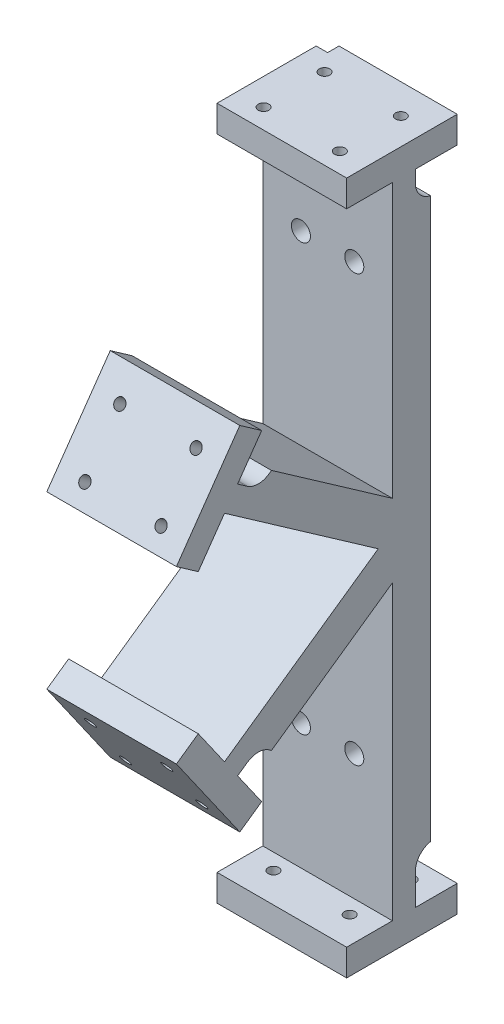
SolidWorks part; units mm, degrees
ref_plane "Front Plane" through (0, 0, 0) normal (0, 0, 1) x (1, 0, 0)
ref_plane "Top Plane" through (0, 0, 0) normal (0, 1, 0) x (1, 0, 0)
ref_plane "Right Plane" through (0, 0, 0) normal (1, 0, 0) x (0, 0, -1)
sketch "Sketch2" plane through (0, 0, 0) normal (0, 0, 1) x (1, 0, 0)
  line L1 (-73.75, 88.375) -> (73.75, 88.375)
  line L2 (-73.75, 88.375) -> (-73.75, -88.375)
  line L3 (-73.75, -88.375) -> (73.75, -88.375)
  line L4 (73.75, 88.375) -> (73.75, -88.375)
  line L5 (-73.75, 88.375) -> (73.75, -88.375) construction
  line L6 (-73.75, -88.375) -> (73.75, 88.375) construction
  point P0 (0, 0)
  dimension "D1" = 147.5
  dimension "D2" = 176.75
extrude "Boss-Extrude1" add sketch "Sketch2" along normal blind 10
sketch "Sketch3" plane through (-73.75, 0, 0) normal (-1, 0, 0) x (0, 0, 1)
  line L0 (0, 88.375) -> (0, -88.375) construction
  line L1 (-7, 88.375) -> (22, 88.375)
  line L2 (-7, 88.375) -> (-7, 73.375)
  line L3 (-7, 73.375) -> (22, 73.375)
  line L4 (22, 88.375) -> (22, 73.375)
  line L5 (10, 88.375) -> (10, -88.375) construction
  line L6 (0, 0) -> (56.8374, 0) construction
  line L7 (22, -88.375) -> (22, -73.375)
  line L8 (-7, -88.375) -> (-7, -73.375)
  line L9 (-7, -88.375) -> (22, -88.375)
  line L10 (-7, -73.375) -> (22, -73.375)
  line L11 (10, 88.375) -> (0, 88.375) construction
  dimension "D1" = 7
  dimension "D2" = 12
  dimension "D3" = 15
  dimension "D4" = 0
extrude "Boss-Extrude2" add sketch "Sketch3" against normal blind 34
ref_plane "Plane1" through (0, 0, 0) normal (1, 0, 0) x (0, 0, -1)
mirror "Mirror1" about plane through (0, 0, 0) normal (1, 0, 0) of "Boss-Extrude2"
sketch "Sketch5" plane through (-73.75, 0, 0) normal (-1, 0, 0) x (0, 0, 1)
  line L0 (10, 73.375) -> (10, -73.375) construction
  line L1 (-35, 0) -> (-35, 43.6802) construction
  line L2 (0, 0) -> (0, 73.375) construction
  line L3 (0, 0) -> (10, 0)
  line L4 (-35, 0) -> (0, 0) construction
  line L5 (-7, 88.375) -> (22, 88.375)
  line L6 (-7, 88.375) -> (-7, 73.375)
  line L7 (-7, 73.375) -> (22, 73.375)
  line L8 (22, 88.375) -> (22, 73.375)
  line L9 (0, 73.375) -> (10, 73.375)
  line L10 (0, 73.375) -> (0, 0)
  line L11 (0, 0) -> (10, 0)
  line L12 (10, 73.375) -> (10, 0)
  line L13 (5, 0) -> (5, -4.9122)
  line L18 (58.2224, 51.916) -> (50.0308, 46.1802)
  line L19 (-7, 73.375) -> (22, 73.375)
  line L20 (-7, 73.375) -> (-7, 63.375)
  line L21 (-7, 63.375) -> (22, 63.375)
  line L22 (22, 73.375) -> (22, 63.375)
  line L23 (50.0308, 46.1802) -> (66.6646, 22.4248)
  line L24 (58.2224, 51.916) -> (74.8561, 28.1606)
  line L25 (74.8561, 28.1606) -> (66.6646, 22.4248)
  line L26 (67.9732, 37.9904) -> (7.8679, -4.0958)
  line L27 (62.2374, 46.1819) -> (2.1321, 4.0958)
  line L28 (2.1321, 4.0958) -> (7.8679, -4.0958)
  line L29 (2.1321, -4.0958) -> (7.8679, 4.0958)
  line L30 (62.2374, -46.1819) -> (2.1321, -4.0958)
  line L31 (67.9732, -37.9904) -> (7.8679, 4.0958)
  line L32 (5, 0) -> (5, 4.9122)
  line L33 (74.8561, -28.1606) -> (66.6646, -22.4248)
  line L34 (58.2224, -51.916) -> (74.8561, -28.1606)
  line L35 (50.0308, -46.1802) -> (66.6646, -22.4248)
  line L36 (58.2224, -51.916) -> (50.0308, -46.1802)
  line L37 (50.0308, 46.1802) -> (66.6646, 22.4248)
  line L38 (-7, 63.375) -> (22, 63.375)
  line L39 (-7, 63.375) -> (-7, 48.375)
  line L40 (-7, 48.375) -> (22, 48.375)
  line L41 (22, 63.375) -> (22, 48.375)
  line L42 (50.0308, 46.1802) -> (37.7436, 37.5766)
  line L43 (37.7436, 37.5766) -> (54.3773, 13.8212)
  line L44 (66.6646, 22.4248) -> (54.3773, 13.8212)
  line L45 (50.0308, -46.1802) -> (66.6646, -22.4248)
  line L46 (66.6646, -22.4248) -> (54.3773, -13.8212)
  line L47 (50.0308, -46.1802) -> (37.7436, -37.5766)
  line L48 (37.7436, -37.5766) -> (54.3773, -13.8212)
  circle A0 centre (-35, 0) radius 110
  point P17 (-35, 0)
  point P31 (5, 0)
  point P34 (5, 0)
  point P51 (5, 0)
  line M9 (10, -73.375) -> (10, 73.375)
  dimension "D3" = 10
  dimension "D1" = 220
  dimension "D2" = 35
  dimension "D5" = 15
  dimension "D4" = 2
  dimension "D6" = 2
extrude "Boss-Extrude3" add sketch "Sketch5" against normal blind 34 contours L31 L26 L23 L27 L12 | L30 L35 L31 L26 M9 | L26 L31 M9 | L44 L23 L26 L43 | L27 L43 L26 L23 | L42 L43 L27 L23 | L48 L47 L35 L30 | L48 L30 L35 L31 | L48 L31 L35 L46 region at (-73.75, 0, 11.2391) region at (-73.75, 15.8458, 27.7303) region at (-73.75, -15.8458, 27.7303) region at (-73.75, 39.0114, 45.8947) region at (-73.75, 32.0486, 50.7701) region at (-73.75, -32.0486, 50.7701) region at (-73.75, -39.0114, 45.8947) region at (-73.75, 23.0379, 57.0795) region at (-73.75, -23.0379, 57.0795)
sketch "Sketch8" plane through (0, 0, 22) normal (0, 0, 1) x (1, 0, 0)
  line L1 (73.75, 88.375) -> (-39.75, 88.375)
  line L2 (73.75, 88.375) -> (73.75, -88.375)
  line L3 (73.75, -88.375) -> (-39.75, -88.375)
  line L4 (-39.75, 88.375) -> (-39.75, -88.375)
extrude "Cut-Extrude1" cut sketch "Sketch8" against normal blind 30
sketch "Sketch9" plane through (0, 0, 0) normal (0, 0, -1) x (-1, 0, 0)
  line L0 (39.75, 73.375) -> (39.75, -73.375) construction
  line L4 (39.75, 73.375) -> (73.75, 73.375) construction
  line L6 (0, 0) -> (126.3955, 0) construction
  line L8 (39.75, -73.375) -> (73.75, -73.375) construction
  circle A0 centre (49.75, 58.375) radius 2.5
  circle A2 centre (63.75, 58.375) radius 2.5
  circle A5 centre (49.75, -53.375) radius 2.5
  circle A6 centre (63.75, -53.375) radius 2.5
  dimension "D1" = 5
  dimension "D2" = 14
  dimension "D3" = 10
  dimension "D4" = 15
  dimension "D6" = 5
  dimension "D7" = 20
  dimension "D8" = 10
  dimension "D5" = 2
  dimension "D9" = 2
extrude "Cut-Extrude2" cut sketch "Sketch9" against normal through all
sketch "Sketch10" plane through (0, 0, -7) normal (0, 0, -1) x (-1, 0, 0)
  line L1 (73.75, 88.375) -> (70.75, 88.375)
  line L2 (73.75, 88.375) -> (73.75, 85.375)
  line L3 (73.75, 85.375) -> (70.75, 85.375)
  line L4 (70.75, 88.375) -> (70.75, 85.375)
  dimension "D1" = 3
  dimension "D2" = 3
extrude "Cut-Extrude3" cut sketch "Sketch10" against normal blind 3
sketch "Sketch11" plane through (0, 88.375, 0) normal (0, 1, 0) x (1, 0, 0)
  line L0 (-39.75, -22) -> (-39.75, 7) construction
  line L1 (-39.75, -22) -> (-73.75, -22) construction
  circle A0 centre (-46.75, -16.8) radius 1.4
  circle A1 centre (-66.75, -16.8) radius 1.4
  circle A2 centre (-66.75, -0.8) radius 1.4
  circle A3 centre (-46.75, -0.8) radius 1.4
  dimension "D1" = 7
  dimension "D2" = 2.8
  dimension "D3" = 5.2
  dimension "D4" = 2
  dimension "D5" = 2
extrude "Cut-Extrude4" cut sketch "Sketch11" against normal blind 10
ref_plane "Plane2" through (0, 0, 0) normal (0, -1, 0) x (-1, 0, 0)
sketch "Sketch12" plane through (0, -88.375, 0) normal (0, -1, 0) x (1, 0, 0)
  line L0 (-39.75, -7) -> (-73.75, -7) construction
  line L1 (-39.75, -7) -> (-39.75, 22) construction
  circle A0 centre (-46.75, -1.8) radius 1.4
  circle A1 centre (-66.75, -1.8) radius 1.4
  circle A2 centre (-66.75, 14.2) radius 1.4
  circle A3 centre (-46.75, 14.2) radius 1.4
  dimension "D1" = 5.2
  dimension "D2" = 7
  dimension "D3" = 2
  dimension "D4" = 2
extrude "Cut-Extrude5" cut sketch "Sketch12" against normal blind 10
sketch "Sketch13" plane through (0, 38.6996, 55.2688) normal (0, 0.5736, 0.8192) x (1, 0, 0)
  line L0 (-39.75, -19.8679) -> (-73.75, -19.8679) construction
  line L1 (-39.75, 9.1321) -> (-39.75, -19.8679) construction
  circle A0 centre (-46.75, -14.6679) radius 1.4
  circle A1 centre (-66.75, -14.6679) radius 1.4
  circle A2 centre (-66.75, 1.3321) radius 1.4
  circle A3 centre (-46.75, 1.3321) radius 1.4
  dimension "D1" = 2.8
  dimension "D2" = 5.2
  dimension "D3" = 7
  dimension "D4" = 2
  dimension "D5" = 2
extrude "Cut-Extrude6" cut sketch "Sketch13" against normal blind 10
sketch "Sketch14" plane through (0, -38.6996, 55.2688) normal (0, -0.5736, 0.8192) x (1, 0, 0)
  line L0 (-39.75, -9.1321) -> (-73.75, -9.1321) construction
  line L1 (-39.75, -9.1321) -> (-39.75, 19.8679) construction
  circle A0 centre (-46.75, -3.9321) radius 1.4
  circle A1 centre (-66.75, -3.9321) radius 1.4
  circle A2 centre (-66.75, 12.0679) radius 1.4
  circle A3 centre (-46.75, 12.0679) radius 1.4
  dimension "D1" = 5.2
  dimension "D2" = 7
  dimension "D3" = 2
  dimension "D4" = 2
extrude "Cut-Extrude7" cut sketch "Sketch14" against normal blind 10
sketch "Sketch15" plane through (-73.75, 0, 0) normal (-1, 0, 0) x (0, 0, 1)
  line L0 (22, 73.375) -> (22, 88.375) construction
  line L1 (-7, 73.375) -> (4, 73.375)
  line L2 (-7, 73.375) -> (-7, 81.375)
  line L3 (-7, 81.375) -> (4, 81.375)
  line L4 (4, 73.375) -> (4, 81.375)
  line L5 (10, 73.375) -> (22, 73.375)
  line L6 (10, 73.375) -> (10, 81.375)
  line L7 (10, 81.375) -> (22, 81.375)
  line L8 (22, 73.375) -> (22, 81.375)
  line L9 (0, 0) -> (-24.7183, 0) construction
  line L10 (-6.6, 0) -> (6.6, 0) construction
  line L11 (22, -73.375) -> (22, -81.375)
  line L12 (10, -81.375) -> (22, -81.375)
  line L13 (10, -73.375) -> (10, -81.375)
  line L14 (10, -73.375) -> (22, -73.375)
  line L15 (4, -73.375) -> (4, -81.375)
  line L16 (-7, -81.375) -> (4, -81.375)
  line L17 (-7, -73.375) -> (-7, -81.375)
  line L18 (-7, -73.375) -> (4, -73.375)
  dimension "D1" = 11
  dimension "D2" = 8
  dimension "D3" = 8
extrude "Cut-Extrude8" cut sketch "Sketch15" against normal through all
sketch "Sketch16" plane through (-73.75, 0, 0) normal (-1, 0, 0) x (0, 0, 1)
  line L0 (41.7586, 31.8425) -> (37.7436, 37.5766)
  line L1 (37.7436, 37.5766) -> (44.0529, 28.5659)
  line L2 (44.0529, 28.5659) -> (50.6061, 33.1545)
  line L3 (50.6061, 33.1545) -> (44.2968, 42.1652)
  line L4 (50.0308, 46.1802) -> (37.7436, 37.5766) construction
  line L5 (44.2968, 42.1652) -> (37.7436, 37.5766)
  line L6 (47.4944, 23.651) -> (54.3773, 13.8212)
  line L7 (54.3773, 13.8212) -> (60.9305, 18.4098)
  line L8 (66.6646, 22.4248) -> (54.3773, 13.8212) construction
  line L9 (60.9305, 18.4098) -> (54.0476, 28.2396)
  line L10 (54.0476, 28.2396) -> (47.4944, 23.651)
  line L11 (-55, 0) -> (55, 0) construction
  line L12 (54.0476, -28.2396) -> (47.4944, -23.651)
  line L13 (60.9305, -18.4098) -> (54.0476, -28.2396)
  line L14 (54.3773, -13.8212) -> (60.9305, -18.4098)
  line L15 (47.4944, -23.651) -> (54.3773, -13.8212)
  line L16 (44.2968, -42.1652) -> (37.7436, -37.5766)
  line L17 (50.6061, -33.1545) -> (44.2968, -42.1652)
  line L18 (44.0529, -28.5659) -> (50.6061, -33.1545)
  line L19 (37.7436, -37.5766) -> (44.0529, -28.5659)
  line L20 (41.7586, -31.8425) -> (37.7436, -37.5766)
  line L21 (44.2968, 42.1652) -> (37.7436, 37.5766)
  line M15 (41.7586, -31.8425) -> (37.7436, -37.5766)
  line M16 (37.7436, -37.5766) -> (50.0308, -46.1802)
  line M18 (66.6646, -22.4248) -> (54.3773, -13.8212)
  line M19 (54.3773, -13.8212) -> (47.4944, -23.651)
  line M22 (47.4944, 23.651) -> (54.3773, 13.8212)
  line M23 (54.3773, 13.8212) -> (66.6646, 22.4248)
  line M25 (50.0308, 46.1802) -> (37.7436, 37.5766)
  line M26 (37.7436, 37.5766) -> (41.7586, 31.8425)
  dimension "D1" = 8
  dimension "D2" = 11
  dimension "D3" = 12
  dimension "D4" = 8
extrude "Cut-Extrude9" cut sketch "Sketch16" against normal through all contours L2 L3 L1 M25 M26 | L9 L10 M22 M23 | L13 L12 M18 M19 | L19 L17 L18 M15 M16 region at (-73.75, 35.3656, 44.1748) region at (-73.75, 21.0304, 54.2124) region at (-73.75, -21.0304, 54.2124) region at (-73.75, -35.3656, 44.1748)
fillet "Fillet1" radius 5 4 edges at (-56.75, -73.375, 4) (-56.75, -28.5659, 44.0529) (-56.75, 28.5659, 44.0529) (-56.75, 73.375, 4)
sketch "Sketch17" plane through (0, -88.375, 0) normal (0, -1, 0) x (1, 0, 0)
  line L1 (-73.75, 22) -> (-39.75, 22)
  line L2 (-73.75, 22) -> (-73.75, -7)
  line L3 (-73.75, -7) -> (-39.75, -7)
  line L4 (-39.75, 22) -> (-39.75, -7)
  circle A0 centre (-66.75, 14.2) radius 1.4
  circle A1 centre (-46.75, 14.2) radius 1.4
  circle A2 centre (-46.75, -1.8) radius 1.4
  circle A3 centre (-66.75, -1.8) radius 1.4
  dimension "D1" = 2
  dimension "D2" = 2
extrude "Boss-Extrude4" add sketch "Sketch17" along normal blind 5
sketch "Sketch18" plane through (-73.75, 0, 0) normal (-1, 0, 0) x (0, 0, 1)
  line L0 (22, -93.375) -> (22, -81.375) construction
  line L1 (-7, -81.375) -> (4, -81.375)
  line L2 (-7, -81.375) -> (-7, -86.375)
  line L3 (-7, -86.375) -> (4, -86.375)
  line L4 (4, -81.375) -> (4, -86.375)
  line L5 (10, -81.375) -> (22, -81.375)
  line L6 (10, -81.375) -> (10, -86.375)
  line L7 (10, -86.375) -> (22, -86.375)
  line L8 (22, -81.375) -> (22, -86.375)
  dimension "D1" = 5
  dimension "D2" = 5
  dimension "D3" = 11
extrude "Cut-Extrude10" cut sketch "Sketch18" against normal through all
